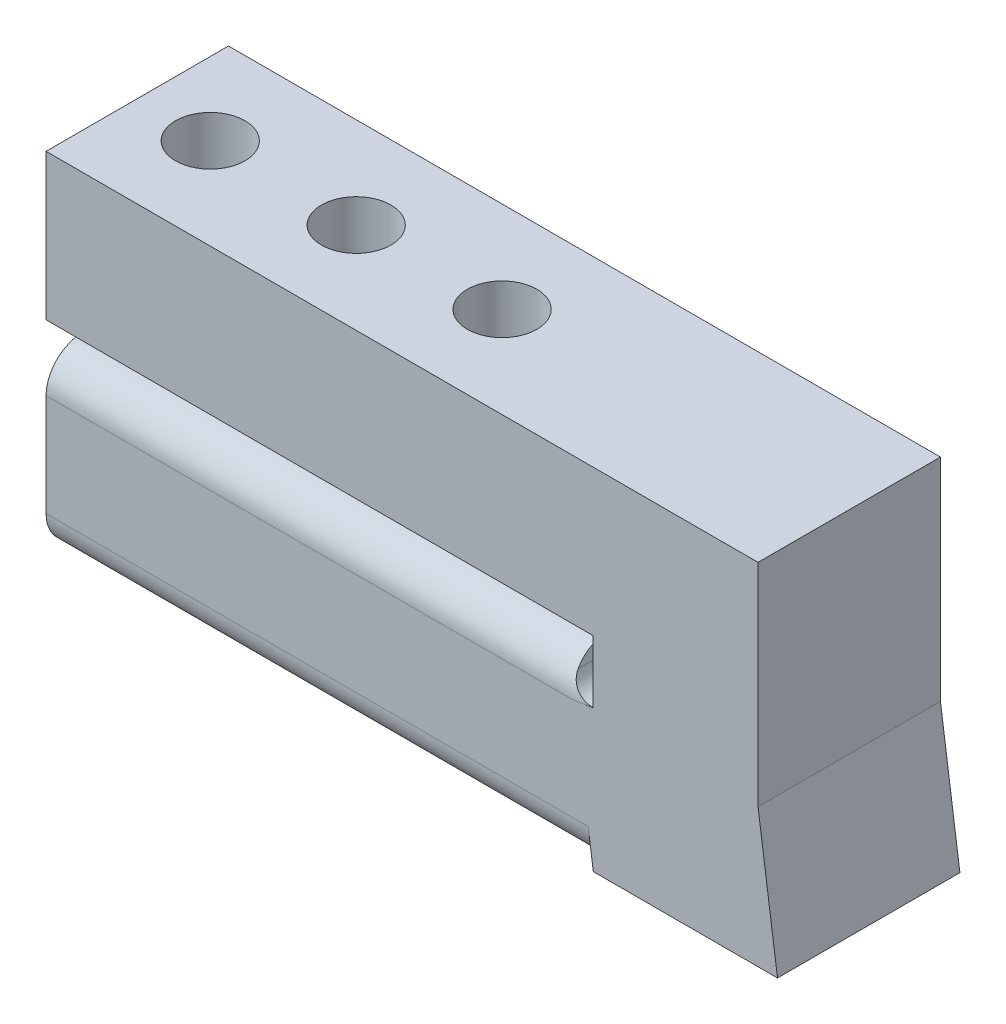
SolidWorks part; units mm, degrees
ref_plane "Front Plane" through (0, 0, 0) normal (0, 0, 1) x (1, 0, 0)
ref_plane "Top Plane" through (0, 0, 0) normal (0, 1, 0) x (1, 0, 0)
ref_plane "Right Plane" through (0, 0, 0) normal (1, 0, 0) x (0, 0, -1)
sketch "Sketch1" plane through (0, 0, 0) normal (0, 0, 1) x (1, 0, 0)
  line L1 (-25, -12.5) -> (25, -12.5)
  line L2 (-25, -12.5) -> (-25, 12.5)
  line L3 (-25, 12.5) -> (25, 12.5)
  line L4 (25, -12.5) -> (25, 12.5)
  line L5 (-25, -12.5) -> (25, 12.5) construction
  line L6 (-25, 12.5) -> (25, -12.5) construction
  point P0 (0, 0)
  dimension "D1" = 50
  dimension "D2" = 25
extrude "Boss-Extrude1" add sketch "Sketch1" along normal blind 25
sketch "Sketch3" plane through (0, 0, 25) normal (0, 0, 1) x (1, 0, 0)
  line L0 (-25, 12.5) -> (-99.2701, 22.938)
  line L1 (-95.93, 46.7044) -> (-25, 36.7359)
  line L2 (-25, 12.5) -> (-58.6977, 12.5) construction
  line L4 (-95.93, 46.7044) -> (-99.2701, 22.938)
  line L6 (0, 36.2664) -> (0, 12.5) construction
  line L7 (25, 12.5) -> (-25, 12.5) construction
  line L8 (-25, 12.5) -> (-21.6598, 36.2664) construction
  line L9 (-25, 12.5) -> (25, 12.5)
  line L10 (25, 12.5) -> (21.5951, 36.7268) construction
  line L11 (95.93, 46.7044) -> (99.2701, 22.938)
  line L13 (25, 12.5) -> (58.6977, 12.5) construction
  line L14 (25, 12.5) -> (99.2701, 22.938)
  line L15 (-25, 36.7359) -> (-25, 31.7359)
  line L16 (-25, 31.7359) -> (25, 31.7359)
  line L17 (0, -13.75) -> (0, 13.75) construction
  line L18 (25, 36.7359) -> (25, 31.7359)
  line L19 (95.93, 46.7044) -> (25, 36.7359)
  point P21 (0, 31.7359)
  dimension "D1" = 8
  dimension "D3" = 75
  dimension "D2" = 24
  dimension "D4" = 5
extrude "Boss-Extrude2" add sketch "Sketch3" against normal up to surface (25 mm away) up to face at (0, 0, 0)
sketch "Sketch4" plane through (-100.5086, 14.1256, 0) normal (-0.9903, 0.1392, 0) x (0, 0, 1)
  line L0 (0, 20.899) -> (25, 20.899) construction
  line L1 (0, 32.899) -> (0, 8.899) construction
  line L2 (25, 32.899) -> (25, 8.899) construction
  circle A0 centre (12.5, 20.899) radius 6.625
  dimension "D1" = 13.25
extrude "Cut-Extrude1" cut sketch "Sketch4" against normal blind 75
mirror "Mirror1" about plane through (0, 0, 0) normal (1, 0, 0) of "Cut-Extrude1"
sketch "Sketch9" plane through (4.5787, 32.5789, 0) normal (0.1392, 0.9903, 0) x (0.9903, -0.1392, 0)
  line L0 (-101.4964, 0) -> (-101.4964, -25) construction
  circle A0 centre (-91.4964, -12.5) radius 3.1
  circle A1 centre (-71.4964, -12.5) radius 3.1
  circle A2 centre (-51.4964, -12.5) radius 3.1
  point P8 (-101.4964, -12.5)
  dimension "D1" = 6.2
  dimension "D2" = 10
  dimension "D3" = 20
  dimension "D4" = 20
extrude "Cut-Extrude6" cut sketch "Sketch9" against normal through all
fillet "Fillet3" radius 5 8 edges at (62.1351, 17.719, 25) (62.1351, 17.719, 0) (60.465, 41.7201, 0) (60.465, 41.7201, 25) (-62.1351, 17.719, 25) (-62.1351, 17.719, 0) (-60.465, 41.7201, 0) (-60.465, 41.7201, 25)
fillet "Fillet5" radius 3 2 edges at (25, 31.7359, 12.5) (-25, 31.7359, 12.5)
sketch "Sketch10" plane through (0, 0, 0) normal (1, 0, 0) x (0, 0, -1)
  line L1 (-35.6486, -49.8313) -> (12.0842, -49.8313)
  line L2 (-35.6486, -49.8313) -> (-35.6486, 57.8365)
  line L3 (-35.6486, 57.8365) -> (12.0842, 57.8365)
  line L4 (12.0842, -49.8313) -> (12.0842, 57.8365)
  line L5 (-35.6486, -49.8313) -> (12.0842, 57.8365) construction
  line L6 (-35.6486, 57.8365) -> (12.0842, -49.8313) construction
  point P0 (-11.7822, 4.0026)
extrude "Cut-Extrude7" cut sketch "Sketch10" along normal blind 100
sketch "Sketch11" plane through (1.2385, 8.8124, 0) normal (-0.1392, -0.9903, 0) x (0.9903, -0.1392, 0)
  line L0 (-27.1991, 0) -> (-23.017, 0) construction
  line L1 (-26.4964, 0) -> (1.7397, 0)
  line L2 (-26.4964, 0) -> (-26.4964, 25)
  line L3 (-26.4964, 25) -> (1.7397, 25)
  line L4 (1.7397, 0) -> (1.7397, 25)
extrude "Cut-Extrude8" cut sketch "Sketch11" along normal through all
sketch "Sketch12" plane through (4.5787, 32.5789, 0) normal (0.1392, 0.9903, 0) x (0.9903, -0.1392, 0)
  line L13 (-26.529, 1.2453) -> (0.9483, 1.2453)
  line L14 (-26.529, 1.2453) -> (-26.529, -26.4542)
  line L15 (-26.529, -26.4542) -> (0.9483, -26.4542)
  line L16 (0.9483, 1.2453) -> (0.9483, -26.4542)
extrude "Cut-Extrude9" cut sketch "Sketch12" against normal blind 5
move or copy body "Body-Move/Copy1" bodies to move or copy 115 copy no rotation origin (-49.6351, 27.8454, 0) rotation axis (0, 0, 1) rotation angle 8
sketch "Sketch13" plane through (0, 35.0779, 0) normal (0, 1, 0) x (1, 0, 0)
  line L4 (-23.1367, -25) -> (-0.5287, -25)
  line L5 (-0.5287, -25) -> (-0.5287, 0)
  line L6 (-0.5287, 0) -> (-23.1367, 0)
  line L7 (-23.1367, 0) -> (-23.1367, -25)
  line L8 (-23.1367, -25) -> (-0.5287, -25)
  line L9 (-0.5287, -25) -> (-0.5287, 0)
  line L10 (-0.5287, 0) -> (-23.1367, 0)
  line L11 (-23.1367, 0) -> (-23.1367, -25)
  dimension "D1" = 0
extrude "Boss-Extrude3" add sketch "Sketch13" along normal blind 29
sketch "Sketch14" plane through (-23.1367, 0, 0) normal (-1, 0, 0) x (0, 0, 1)
  line L0 (25, 64.0779) -> (25, 35.4982) construction
  line L1 (0, 64.0779) -> (25, 64.0779)
  line L2 (0, 64.0779) -> (0, 44.0779)
  line L3 (0, 44.0779) -> (25, 44.0779)
  line L4 (25, 64.0779) -> (25, 44.0779)
  dimension "D1" = 20
extrude "Boss-Extrude4" add sketch "Sketch14" along normal up to surface (74.9674 mm away) up to face at (-98.1041, 21.4529, 12.5)
sketch "Sketch15" plane through (0, 64.0779, 0) normal (0, 1, 0) x (1, 0, 0)
  circle A0 centre (-48.1041, -12.5) radius 3.1 construction
  circle A1 centre (-68.1041, -12.5) radius 3.1 construction
  circle A2 centre (-88.1041, -12.5) radius 3.1 construction
  circle A3 centre (-48.1041, -12.5) radius 3.1
  circle A4 centre (-68.1041, -12.5) radius 3.1
  circle A5 centre (-88.1041, -12.5) radius 3.1
  circle A6 centre (-88.1041, -12.5) radius 4.7625
  circle A7 centre (-68.1041, -12.5) radius 4.7625
  circle A8 centre (-48.1041, -12.5) radius 4.7625
  dimension "D1" = 9.525
extrude "Cut-Extrude10" cut sketch "Sketch15" against normal through all and the other way through all contours A5 | A6 A5 | A7 A4 | A4 | A8 A3 | A3 region at (-48.1041, 64.0779, 12.5) region at (-68.1041, 64.0779, 12.5) region at (-88.1041, 64.0779, 12.5) region at (-92.7319, 64.0779, 12.5) region at (-72.7319, 64.0779, 12.5) region at (-52.7319, 64.0779, 12.5)
